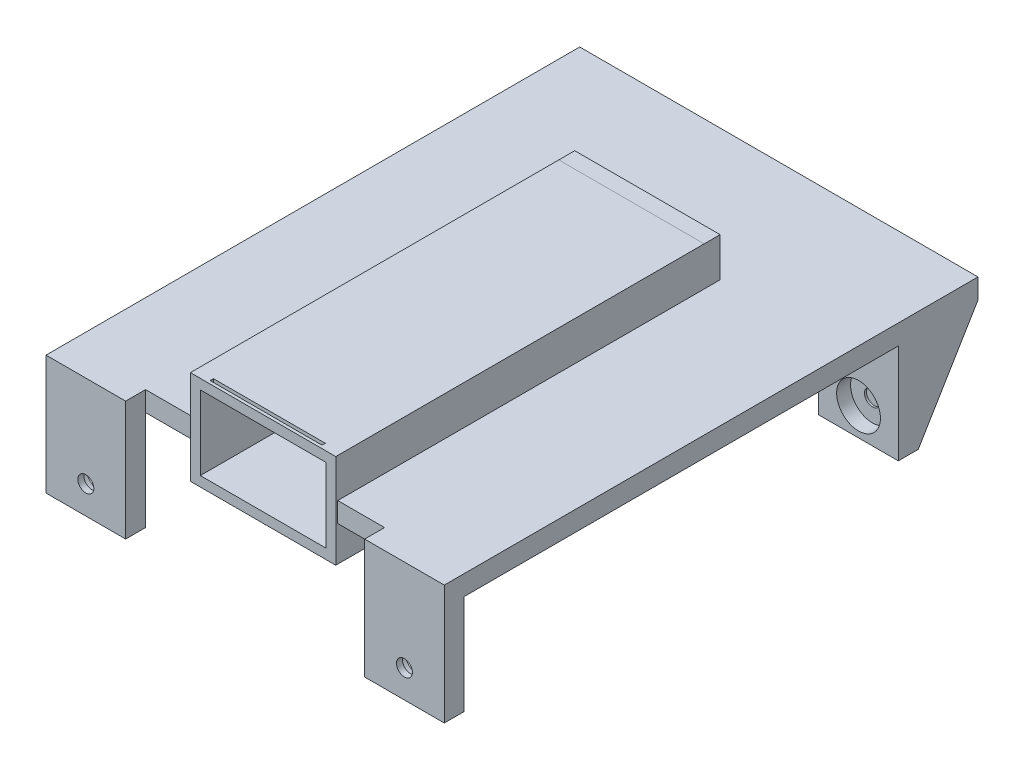
SolidWorks part; units mm, degrees
ref_plane "Front Plane" through (0, 0, 0) normal (0, 0, 1) x (1, 0, 0)
ref_plane "Top Plane" through (0, 0, 0) normal (0, 1, 0) x (1, 0, 0)
ref_plane "Right Plane" through (0, 0, 0) normal (1, 0, 0) x (0, 0, -1)
sketch "Sketch1" plane through (0, 0, 0) normal (0, 1, 0) x (1, 0, 0)
  line L1 (-100, -129) -> (100, -129)
  line L2 (-100, -129) -> (-100, 129)
  line L3 (-100, 129) -> (100, 129)
  line L4 (100, -129) -> (100, 129)
  line L5 (-100, -129) -> (100, 129) construction
  line L6 (-100, 129) -> (100, -129) construction
  point P0 (0, 0)
  dimension "D1" = 200
  dimension "D2" = 258
extrude "Boss-Extrude1" add sketch "Sketch1" along normal blind 10 contours L3 L4 L1 L2
ref_plane "Plane2" through (100, 0, 0) normal (1, 0, 0) x (0, 0, -1)
sketch "Sketch2" plane through (100, 0, 0) normal (1, 0, 0) x (0, 0, -1)
  line L0 (89, 0) -> (89, -50)
  line L1 (-129, 0) -> (129, 0) construction
  line L3 (129, 0) -> (89, 0)
  line L4 (89, -50) -> (99, -50)
  line L5 (99, -50) -> (129, 0)
  dimension "D1" = 50
  dimension "D2" = 40
  dimension "D3" = 10
extrude "Boss-Extrude4" add sketch "Sketch2" against normal blind 40 contours L5 L3 L0 L4
sketch "Sketch5" plane through (0, 0, -89) normal (0, 0, 1) x (1, 0, 0)
  line L0 (80, 0) -> (80, -50) construction
  line L1 (60, 0) -> (100, 0) construction
  line L2 (60, -50) -> (100, -50) construction
  line L3 (60, -36) -> (100, -36) construction
  line L4 (60, 0) -> (60, -50) construction
  line L5 (100, 0) -> (100, -50) construction
  circle A0 centre (80, -36) radius 11
  dimension "D2" = 22
  dimension "D1" = 14
extrude "Cut-Extrude2" cut sketch "Sketch5" against normal blind 7 contours A0
ref_plane "Plane5" through (0, 0, 0) normal (1, 0, 0) x (0, 0, -1)
mirror "Mirror3" about plane through (0, 0, 0) normal (1, 0, 0) of "Cut-Extrude2", "Boss-Extrude4"
sketch "Sketch6" plane through (0, 10, 0) normal (0, 1, 0) x (1, 0, 0)
  line L0 (-100, -129) -> (100, -129)
  line L1 (-100, -129) -> (-100, -139)
  line L2 (100, -129) -> (100, -139)
  line L3 (-100, -139) -> (100, -139)
  line L4 (-100, -129) -> (100, -129) construction
  dimension "D1" = 10
extrude "Boss-Extrude6" add sketch "Sketch6" against normal blind 60
sketch "Sketch7" plane through (0, 0, 139) normal (0, 0, 1) x (1, 0, 0)
  line L0 (-100, -50) -> (100, -50) construction
  line L1 (-60, -50) -> (60, -50)
  line L2 (-60, -50) -> (-60, 10)
  line L3 (-60, 10) -> (60, 10)
  line L4 (60, -50) -> (60, 10)
  line L5 (-100, 10) -> (100, 10) construction
  line L6 (-100, -50) -> (-100, 10) construction
  dimension "D1" = 40
  dimension "D2" = 40
extrude "Cut-Extrude3" cut sketch "Sketch7" against normal blind 10
ref_plane "Plane6" through (0, 0, 20) normal (0, 0, 1) x (1, 0, 0)
mirror "Mirror4" about plane through (0, 0, 0) normal (1, 0, 0) of "Cut-Extrude2" second plane through (0, 0, 20) second plane normal (0, 0, 1)
sketch "Sketch8" plane through (0, 0, 136) normal (0, 0, -1) x (-1, 0, 0)
  circle A0 centre (-80, -36) radius 4
  circle A1 centre (-80, -36) radius 11
  circle A2 centre (-80, -36) radius 11
  dimension "D2" = 8
  dimension "D1" = 0
extrude "Cut-Extrude4" cut sketch "Sketch8" against normal blind 10 contours A0
mirror "Mirror5" about plane through (0, 0, 0) normal (1, 0, 0) of "Cut-Extrude4"
sketch "Sketch9" plane through (0, 0, -96) normal (0, 0, 1) x (1, 0, 0)
  circle A0 centre (-80, -36) radius 4
  circle A1 centre (-80, -36) radius 11
  circle A2 centre (-80, -36) radius 11
  dimension "D2" = 8
  dimension "D1" = 0
extrude "Cut-Extrude6" cut sketch "Sketch9" against normal blind 1 contours A0
mirror "Mirror6" about plane through (0, 0, 0) normal (1, 0, 0) of "Cut-Extrude6"
ref_plane "Plane7" through (0, 0, 130) normal (0, 0, 1) x (1, 0, 0)
sketch "Sketch12" plane through (0, 0, 130) normal (0, 0, 1) x (1, 0, 0)
  line L0 (-60, 0) -> (60, 0) construction
  line L1 (-31.5, -12.6372) -> (31.5, -12.6372)
  line L2 (-31.5, -12.6372) -> (-31.5, 24.6372)
  line L3 (-31.5, 24.6372) -> (31.5, 24.6372)
  line L4 (31.5, -12.6372) -> (31.5, 24.6372)
  line L5 (-31.5, -12.6372) -> (31.5, 24.6372) construction
  line L6 (-31.5, 24.6372) -> (31.5, -12.6372) construction
  line L8 (60, 0) -> (60, 10) construction
  line L9 (-36.5, -17.6372) -> (36.5, -17.6372)
  line L10 (-36.5, -17.6372) -> (-36.5, 29.6372)
  line L11 (-36.5, 29.6372) -> (36.5, 29.6372)
  line L12 (36.5, -17.6372) -> (36.5, 29.6372)
  line L13 (-36.5, -17.6372) -> (36.5, 29.6372) construction
  line L14 (-36.5, 29.6372) -> (36.5, -17.6372) construction
  point P0 (0, 6)
  point P7 (0, 0)
  point P10 (0, 6)
  dimension "D1" = 6
  dimension "D2" = 63
  dimension "D3" = 37.2744
  dimension "D4" = 60
  dimension "D5" = 5
  dimension "D6" = 5
extrude "Boss-Extrude8" add sketch "Sketch12" against normal blind 185 separate body
ref_plane "Plane8" through (0, 0, 129) normal (0, 0, 1) x (1, 0, 0)
sketch "Sketch14" plane through (0, 0, 129) normal (0, 0, 1) x (1, 0, 0)
  line L1 (-31.5, -11.8424) -> (31.5, -11.8424)
  line L2 (-31.5, -11.8424) -> (-31.5, 11.8424)
  line L3 (-31.5, 11.8424) -> (31.5, 11.8424)
  line L4 (31.5, -11.8424) -> (31.5, 11.8424)
  line L5 (-31.5, -11.8424) -> (31.5, 11.8424) construction
  line L6 (-31.5, 11.8424) -> (31.5, -11.8424) construction
  line L7 (31.5, -12.6372) -> (31.5, 24.6372) construction
  line L8 (-31.5, 24.6372) -> (-31.5, -12.6372) construction
  line L9 (60, 10) -> (-60, 10) construction
  line L10 (-31.5, -12.6372) -> (31.5, -12.6372) construction
  dimension "D1" = 0
  dimension "D2" = 0
  dimension "D3" = 1.8424
  dimension "D4" = 0.7948
extrude "Cut-Extrude7" cut sketch "Sketch14" against normal blind 184 contours L3 L4 L1 L2
ref_plane "Plane9" through (0, -17.6372, 0) normal (0, -1, 0) x (-1, 0, 0)
sketch "Sketch15" plane through (0, -17.6372, 0) normal (0, -1, 0) x (-1, 0, 0)
  line L0 (-36.5, 55) -> (36.5, 55)
  line L1 (-36.5, 55) -> (-36.5, 63)
  line L2 (36.5, 55) -> (36.5, 63)
  line L3 (-36.5, 63) -> (36.5, 63)
  dimension "D1" = 8
extrude "Cut-Extrude8" cut sketch "Sketch15" against normal blind 184
sketch "Sketch16" plane through (0, -17.6372, 0) normal (0, -1, 0) x (-1, 0, 0)
  line L0 (-36.5, 55) -> (36.5, 55)
  line L1 (-36.5, 55) -> (-36.5, 63)
  line L2 (36.5, 55) -> (36.5, 63)
  line L3 (-36.5, 63) -> (36.5, 63)
  dimension "D1" = 8
extrude "Boss-Extrude9" add sketch "Sketch16" against normal blind 47.27 contours L0 L2 L3 L1
ref_axis "Axis1" through (0, 29.6372, -141.3) along (0, 0, 1)
sketch "Sketch17" plane through (0, 29.6372, 0) normal (0, 1, 0) x (1, 0, 0)
  line L0 (36.5, -130) -> (-36.5, -130) construction
  line L1 (28.0968, -126.8422) -> (-28.0968, -126.8422)
  line L2 (28.0968, -126.8422) -> (28.0968, -128.4957)
  line L3 (28.0968, -128.4957) -> (-28.0968, -128.4957)
  line L4 (-28.0968, -126.8422) -> (-28.0968, -128.4957)
  line L5 (28.0968, -126.8422) -> (-28.0968, -128.4957) construction
  line L6 (28.0968, -128.4957) -> (-28.0968, -126.8422) construction
  line L8 (-36.5, 55) -> (-36.5, -130) construction
  point P0 (0, -127.669)
  dimension "D1" = 1.5043
  dimension "D2" = 3.1578
  dimension "D3" = 56.1935
  dimension "D4" = 8.4032
extrude "Cut-Extrude9" cut sketch "Sketch17" against normal blind 7.27
